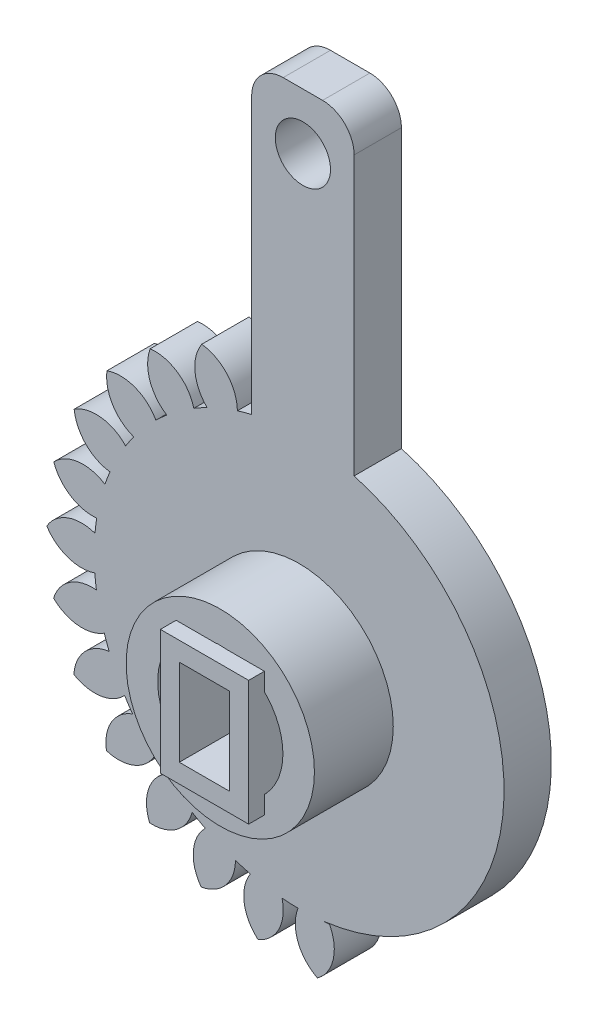
SolidWorks part; units mm, degrees
ref_plane "Front Plane" through (0, 0, 0) normal (0, 0, 1) x (1, 0, 0)
ref_plane "Top Plane" through (0, 0, 0) normal (0, 1, 0) x (1, 0, 0)
ref_plane "Right Plane" through (0, 0, 0) normal (1, 0, 0) x (0, 0, -1)
ref_plane "Plane1" through (0, 0, 5) normal (0, 0, 1) x (1, 0, 0)
ref_plane "Plane2" through (0, 0, 7) normal (0, 0, 1) x (1, 0, 0)
ref_plane "Plane3" through (0, 0, 3) normal (0, 0, 1) x (1, 0, 0)
sketch "Sketch1" plane through (0, 0, 5) normal (0, 0, 1) x (1, 0, 0)
  circle A0 centre (0, 20.9252) radius 3.9726
  circle A1 centre (0, 20.9252) radius 5
  dimension "D1" = 10
sketch "Sketch3" plane through (0, 0, 7) normal (0, 0, 1) x (1, 0, 0)
  line L0 (-3.9726, 20.9252) -> (15.3734, 20.9252) construction
  line L1 (0, 24.8978) -> (0, 8.7425) construction
  line L3 (-1.6, 23.6752) -> (1.6, 23.6752)
  line L4 (-1.6, 23.6752) -> (-1.6, 18.1752)
  line L5 (-1.6, 18.1752) -> (1.6, 18.1752)
  line L6 (1.6, 23.6752) -> (1.6, 18.1752)
  dimension "D1" = 3.2
  dimension "D2" = 5.5
  dimension "D3" = 1.6
  dimension "D4" = 2.75
extrude "Boss-Extrude1" add sketch "Sketch1" along normal blind 6 contours A0
shell "Shell1" thickness 2 removed face at (3.9726, 20.9252, 11) outward yes
extrude "Boss-Extrude2" add sketch "Sketch3" along normal blind 5 separate body
shell "Shell2" thickness 1.2 removed face at (0, 20.9252, 12) outward yes
sketch "Sketch7" plane through (0, 0, 3) normal (0, 0, -1) x (-1, 0, 0)
  line L0 (0, 14.9526) -> (0, 35.2199) construction
  line L1 (5.9726, 20.9252) -> (-26.894, 20.9252) construction
  circle A0 centre (0, 20.9252) radius 5.9726 construction
sketch "Sketch5" plane through (0, 0, 3) normal (0, 0, 1) x (1, 0, 0)
  line L1 (0, 14.9526) -> (0, 35.2199) construction
  line L2 (-5.9726, 20.9252) -> (26.894, 20.9252) construction
  circle A0 centre (0, 20.9252) radius 13
extrude "Boss-Extrude3" add sketch "Sketch5" along normal blind 3 contours A0
sketch "Sketch6" plane through (0, 0, 3) normal (0, 0, 1) x (1, 0, 0)
  line L1 (-3.01, 33.0817) -> (3.49, 33.0817)
  line L2 (-3.01, 33.0817) -> (-3.01, 53.0817)
  line L3 (-3.01, 53.0817) -> (3.49, 53.0817)
  line L4 (3.49, 33.0817) -> (3.49, 53.0817)
  dimension "D1" = 20
  dimension "D2" = 6.5
extrude "Boss-Extrude4" add sketch "Sketch6" along normal up to surface (3 mm away) up to face at (5.9726, 20.9252, 6)
sketch "Sketch8" plane through (0, 0, 3) normal (0, 0, 1) x (1, 0, 0)
  line L0 (-5.7594, 32.4645) -> (-3.9194, 33.1775)
  line L1 (0.24, 53.0817) -> (0.24, -3.388) construction
  line L2 (3.49, 53.0817) -> (-3.01, 53.0817) construction
  line L3 (13, 20.9252) -> (-7.0281, 20.9252) construction
  line L20 (-8.2588, 30.7699) -> (-6.6328, 31.8881)
  line L21 (-10.3, 28.5446) -> (-8.9758, 30.0076)
  line L22 (-11.7731, 25.9085) -> (-10.8219, 27.6375)
  line L23 (-12.5985, 23.0038) -> (-12.0717, 24.9055)
  line L24 (-12.7318, 19.987) -> (-12.6577, 21.9589)
  line L25 (-12.1657, 17.0208) -> (-12.5485, 18.9567)
  line L26 (-10.9309, 14.2651) -> (-11.7498, 16.0605)
  line L27 (-9.0939, 11.8684) -> (-10.3047, 13.4266)
  line L28 (-6.7536, 9.96) -> (-8.2911, 11.197)
  line L29 (-4.0364, 8.6427) -> (-5.8177, 9.4918)
  line L30 (-1.0886, 7.9876) -> (-3.0177, 8.403)
  line L31 (1.9309, 8.03) -> (-0.042, 7.9892)
  arc A0 (-3.9194, 33.1775) -> (-6.1748, 35.8519) centre (-6.4822, 33.3045) ccw
  arc A3 (-6.1748, 35.8519) -> (-5.7594, 32.4645) centre (-4.0035, 34.399) ccw
  arc A4 (-3.01, 33.572) -> (3.49, 33.448) centre (0, 20.9252) ccw construction
  arc A53 (-6.6328, 31.8881) -> (-9.4442, 33.9702) centre (-9.1558, 31.4205) ccw
  arc A54 (-9.4442, 33.9702) -> (-8.2588, 30.7699) centre (-6.9964, 33.0572) ccw
  arc A55 (-8.9758, 30.0076) -> (-12.1916, 31.3853) centre (-11.323, 28.9708) ccw
  arc A56 (-12.1916, 31.3853) -> (-10.3, 28.5446) centre (-9.5992, 31.0614) ccw
  arc A57 (-10.8219, 27.6375) -> (-14.2687, 28.2364) centre (-12.8667, 26.0873) ccw
  arc A58 (-14.2687, 28.2364) -> (-11.7731, 25.9085) centre (-11.6715, 28.5191) ccw
  arc A59 (-12.0717, 24.9055) -> (-15.5637, 24.6934) centre (-13.7039, 22.9256) ccw
  arc A60 (-15.5637, 24.6934) -> (-12.5985, 23.0038) centre (-13.1017, 25.5674) ccw
  arc A61 (-12.6577, 21.9589) -> (-16.0067, 20.9472) centre (-13.7893, 19.656) ccw
  arc A62 (-16.0067, 20.9472) -> (-12.7318, 19.987) centre (-13.8126, 22.3655) ccw
  arc A63 (-12.5485, 18.9567) -> (-15.5739, 17.1999) centre (-13.1185, 16.4548) ccw
  arc A64 (-15.5739, 17.1999) -> (-12.1657, 17.0208) centre (-13.766, 19.0859) ccw
  arc A65 (-11.7498, 16.0605) -> (-14.2885, 13.6534) centre (-11.7274, 13.4946) ccw
  arc A66 (-14.2885, 13.6534) -> (-10.9309, 14.2651) centre (-12.9643, 15.9055) ccw
  arc A67 (-10.3047, 13.4266) -> (-12.2199, 10.4989) centre (-9.6912, 10.9351) ccw
  arc A68 (-12.2199, 10.4989) -> (-9.0939, 11.8684) centre (-11.4507, 12.9957) ccw
  arc A69 (-8.2911, 11.197) -> (-9.4795, 7.9065) centre (-7.1197, 8.9141) ccw
  arc A70 (-9.4795, 7.9065) -> (-6.7536, 9.96) centre (-9.3069, 10.5134) ccw
  arc A71 (-5.8177, 9.4918) -> (-6.2152, 6.016) centre (-4.1513, 7.5406) ccw
  arc A72 (-6.2152, 6.016) -> (-4.0364, 8.6427) centre (-6.6484, 8.5924) ccw
  arc A73 (-3.0177, 8.403) -> (-2.6029, 4.9292) centre (-0.9462, 6.8887) ccw
  arc A74 (-2.6029, 4.9292) -> (-1.0886, 7.9876) centre (-3.6186, 7.3362) ccw
  arc A75 (-0.042, 7.9892) -> (1.1627, 4.7047) centre (2.3228, 6.9935) ccw
  arc A76 (1.1627, 4.7047) -> (1.9309, 8.03) centre (-0.3808, 6.8127) ccw
  point P26 (0.24, 20.9252)
  point P78 (0.24, 20.9252)
  point P153 (0.24, 20.9252)
  dimension "D1" = 13
extrude "Boss-Extrude5" add sketch "Sketch8" along normal up to surface (3 mm away) up to face at (0.118, 36.9003, 6)
sketch "Sketch9" plane through (0, 0, 3) normal (0, 0, -1) x (-1, 0, 0)
  line L0 (-0.24, 53.0817) -> (-0.24, 49.0919) construction
  line L1 (-3.49, 53.0817) -> (3.01, 53.0817) construction
  circle A0 centre (-0.24, 49.5317) radius 1.75
  dimension "D1" = 3.55
extrude "Cut-Extrude1" cut sketch "Sketch9" against normal up to surface (3 mm away) up to face at (-7.665, 20.7603, 6)
fillet "Fillet1" radius 2 2 edges at (3.49, 53.0817, 4.5) (-3.01, 53.0817, 4.5)
